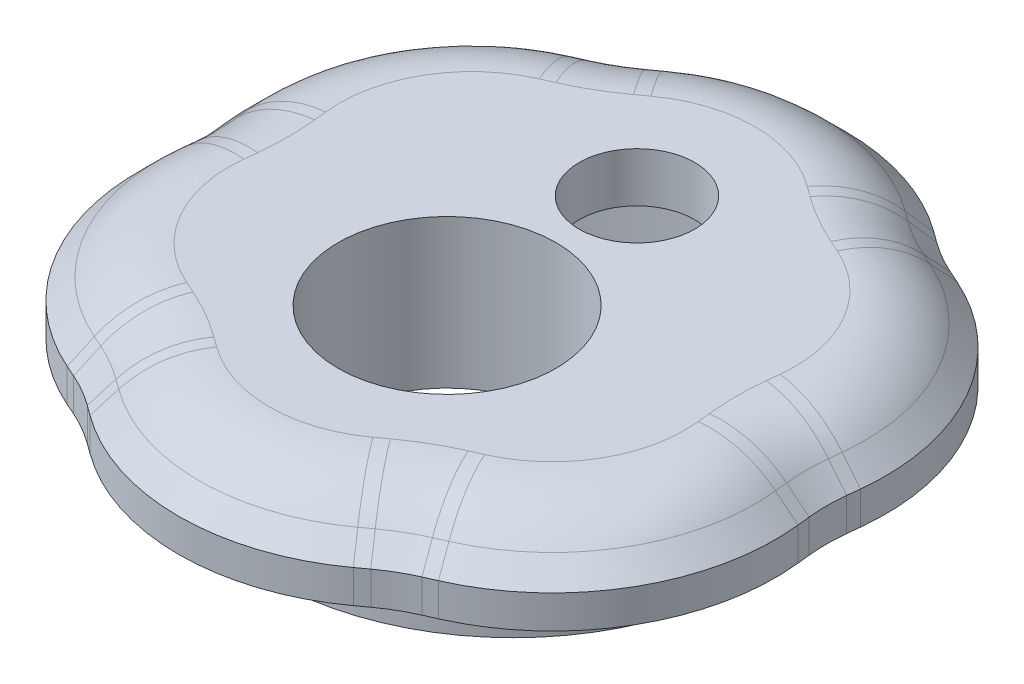
SolidWorks part; units mm, degrees
ref_plane "前基準面" through (0, 0, 0) normal (0, 0, 1) x (1, 0, 0)
ref_plane "上基準面" through (0, 0, 0) normal (0, 1, 0) x (1, 0, 0)
ref_plane "右基準面" through (0, 0, 0) normal (1, 0, 0) x (0, 0, -1)
sketch "草圖1" plane through (0, 0, 0) normal (0, 1, 0) x (1, 0, 0)
  line L14 (-20.7719, 1.7234) -> (-20.6902, 0.9708)
  line L19 (-20.6902, -0.9731) -> (-20.7719, -1.7257)
  line L20 (-11.9129, -17.0699) -> (-11.2203, -17.3754)
  line L21 (-9.5368, -18.3474) -> (-8.926, -18.7945)
  line L22 (8.7921, -18.7945) -> (9.4029, -18.3474)
  line L23 (11.0864, -17.3754) -> (11.779, -17.0699)
  line L24 (20.638, -1.7257) -> (20.5563, -0.9731)
  line L25 (20.5563, 0.9708) -> (20.638, 1.7234)
  line L26 (11.779, 17.0676) -> (11.0864, 17.3731)
  line L27 (9.4029, 18.3451) -> (8.7921, 18.7921)
  line L28 (-8.926, 18.7921) -> (-9.5368, 18.3451)
  line L29 (-11.2203, 17.3731) -> (-11.9129, 17.0676)
  arc A13 (-11.9129, 17.0676) -> (-20.7719, 1.7234) centre (-5.8597, 3.3433) ccw
  arc A14 (-20.6902, 0.9708) -> (-20.6902, -0.9731) centre (-29.6375, -0.0012) cw
  arc A15 (-20.7719, -1.7257) -> (-11.9129, -17.0699) centre (-5.8597, -3.3456) ccw
  arc A16 (-9.5368, -18.3474) -> (-11.2203, -17.3754) centre (-14.8522, -25.61) ccw
  arc A17 (-8.926, -18.7945) -> (8.7921, -18.7945) centre (-0.0669, -6.69) ccw
  arc A18 (11.0864, -17.3754) -> (9.4029, -18.3474) centre (14.7184, -25.61) ccw
  arc A19 (11.779, -17.0699) -> (20.638, -1.7257) centre (5.7258, -3.3456) ccw
  arc A20 (20.5563, 0.9708) -> (20.5563, -0.9731) centre (29.5037, -0.0012) ccw
  arc A21 (20.638, 1.7234) -> (11.779, 17.0676) centre (5.7258, 3.3433) ccw
  arc A22 (9.4029, 18.3451) -> (11.0864, 17.3731) centre (14.7184, 25.6077) ccw
  arc A23 (8.7921, 18.7921) -> (-8.926, 18.7921) centre (-0.0669, 6.6877) ccw
  arc A24 (-11.2203, 17.3731) -> (-9.5368, 18.3451) centre (-14.8522, 25.6077) ccw
  point P20 (-0.0509, -0.0012)
  dimension "D1" = 6.6888
  dimension "D2" = 6.69
extrude "填料-伸長1" add sketch "草圖1" along normal blind 3
chamfer "導角1" distance 4.5 angle 45 24 edges at (-0.0669, 3, -21.6877) (-9.2314, 3, -18.5686) (9.0975, 3, -18.5686) (-10.3522, 3, -17.8135) (10.2184, 3, -17.8135) (-11.5666, 3, -17.2204) (11.4327, 3, -17.2204) (-18.85, 3, -10.8433) (18.7161, 3, -10.8433) (-20.731, 3, -1.3471) (20.5972, 3, -1.3471) (-20.6375, 3, 0.0012) (20.5037, 3, 0.0012) (-20.731, 3, 1.3494) (20.5972, 3, 1.3494) (-18.85, 3, 10.8456) (18.7161, 3, 10.8456) (-11.5666, 3, 17.2227) (11.4327, 3, 17.2227) (-10.3522, 3, 17.8158) (10.2184, 3, 17.8158) (-9.2314, 3, 18.5709) (9.0975, 3, 18.5709) (-0.0669, 3, 21.69)
sketch "草圖3" plane through (0, 0, 0) normal (0, -1, 0) x (1, 0, 0)
  circle A0 centre (0, 0) radius 14.75
  circle A1 centre (0, 0) radius 14
  dimension "D1" = 29.5
  dimension "D2" = 28
extrude "填料-伸長2" add sketch "草圖3" along normal blind 6
fillet "圓角1" radius 6 24 edges at (-6.5737, 3, 14.9396) (-8.1022, 3, 13.9187) (-9.7506, 3, 13.1054) (-14.9529, 3, 8.5956) (-16.2574, 3, 1.8354) (-16.1375, 3, 0.0012) (-16.2574, 3, -1.833) (-14.9529, 3, -8.5933) (-9.7506, 3, -13.1031) (-8.1022, 3, -13.9164) (-6.5737, 3, -14.9373) (-0.0669, 3, -17.1877) (6.4398, 3, -14.9373) (7.9684, 3, -13.9164) (9.6167, 3, -13.1031) (14.819, 3, -8.5933) (16.1235, 3, -1.833) (16.0037, 3, 0.0012) (16.1235, 3, 1.8354) (14.819, 3, 8.5956) (9.6167, 3, 13.1054) (7.9684, 3, 13.9187) (6.4398, 3, 14.9396) (-0.0669, 3, 17.19)
sketch "草圖4" plane through (0, 3, 0) normal (0, 1, 0) x (1, 0, 0)
  circle A0 centre (0, -4) radius 6.6
  circle A1 centre (0, 7.5) radius 3.5
  dimension "D1" = 4
  dimension "D2" = 7
  dimension "D3" = 11.5
  dimension "D4" = 13.2
extrude "除料-伸長1" cut sketch "草圖4" against normal blind 10
sketch "草圖5" plane through (0, 0, 0) normal (0, -1, 0) x (1, 0, 0)
  circle A0 centre (0, 4) radius 6.6
  circle A1 centre (0, 4) radius 7.5
  dimension "D1" = 15
extrude "填料-伸長3" add sketch "草圖5" along normal blind 6
sketch "草圖6" plane through (0, 0, 0) normal (0, -1, 0) x (1, 0, 0)
  line L12 (-8.0603, -16.3276) -> (-7.4495, -16.7747)
  line L13 (7.3156, -16.7747) -> (7.9264, -16.3276)
  line L14 (10.0775, -15.0857) -> (10.7701, -14.7802)
  line L15 (18.1527, -1.9933) -> (18.0709, -1.2408)
  line L16 (18.0709, 1.2431) -> (18.1527, 1.9957)
  line L17 (10.7701, 14.7825) -> (10.0775, 15.088)
  line L18 (7.9264, 16.33) -> (7.3156, 16.777)
  line L19 (-7.4495, 16.777) -> (-8.0603, 16.33)
  line L20 (-10.2114, 15.088) -> (-10.904, 14.7825)
  line L21 (-18.2865, 1.9957) -> (-18.2048, 1.2431)
  line L22 (-18.2048, -1.2408) -> (-18.2865, -1.9933)
  line L23 (-10.904, -14.7802) -> (-10.2114, -15.0857)
  line L24 (-8.6509, -17.1346) -> (-8.0401, -17.5817)
  line L25 (7.9062, -17.5817) -> (8.517, -17.1346)
  line L26 (10.4811, -16.0007) -> (11.1737, -15.6952)
  line L27 (19.1468, -1.8853) -> (19.0651, -1.1328)
  line L28 (19.0651, 1.1351) -> (19.1468, 1.8877)
  line L29 (11.1737, 15.6975) -> (10.4811, 16.003)
  line L30 (8.517, 17.1369) -> (7.9062, 17.584)
  line L31 (-8.0401, 17.584) -> (-8.6509, 17.1369)
  line L32 (-10.615, 16.003) -> (-11.3076, 15.6975)
  line L33 (-19.2807, 1.8877) -> (-19.1989, 1.1351)
  line L34 (-19.1989, -1.1328) -> (-19.2807, -1.8853)
  line L35 (-11.3076, -15.6952) -> (-10.615, -16.0007)
  line L36 (-8.6509, -17.1346) -> (-8.0401, -17.5817)
  line L37 (7.9062, -17.5817) -> (8.517, -17.1346)
  line L38 (10.4811, -16.0007) -> (11.1737, -15.6952)
  line L39 (19.1468, -1.8853) -> (19.0651, -1.1328)
  line L40 (19.0651, 1.1351) -> (19.1468, 1.8877)
  line L41 (11.1737, 15.6975) -> (10.4811, 16.003)
  line L42 (8.517, 17.1369) -> (7.9062, 17.584)
  line L43 (-8.0401, 17.584) -> (-8.6509, 17.1369)
  line L44 (-10.615, 16.003) -> (-11.3076, 15.6975)
  line L45 (-19.2807, 1.8877) -> (-19.1989, 1.1351)
  line L46 (-19.1989, -1.1328) -> (-19.2807, -1.8853)
  line L47 (-11.3076, -15.6952) -> (-10.615, -16.0007)
  arc A12 (-7.4495, -16.7747) -> (7.3156, -16.7747) centre (-0.0669, -6.6877) ccw
  arc A13 (10.0775, -15.0857) -> (7.9264, -16.3276) centre (14.7184, -25.6077) ccw
  arc A14 (10.7701, -14.7802) -> (18.1527, -1.9933) centre (5.7258, -3.3433) ccw
  arc A15 (18.0709, 1.2431) -> (18.0709, -1.2408) centre (29.5037, 0.0012) ccw
  arc A16 (18.1527, 1.9957) -> (10.7701, 14.7825) centre (5.7258, 3.3456) ccw
  arc A17 (7.9264, 16.33) -> (10.0775, 15.088) centre (14.7184, 25.61) ccw
  arc A18 (7.3156, 16.777) -> (-7.4495, 16.777) centre (-0.0669, 6.69) ccw
  arc A19 (-10.2114, 15.088) -> (-8.0603, 16.33) centre (-14.8522, 25.61) ccw
  arc A20 (-10.904, 14.7825) -> (-18.2865, 1.9957) centre (-5.8597, 3.3456) ccw
  arc A21 (-18.2048, -1.2408) -> (-18.2048, 1.2431) centre (-29.6375, 0.0012) ccw
  arc A22 (-18.2865, -1.9933) -> (-10.904, -14.7802) centre (-5.8597, -3.3433) ccw
  arc A23 (-8.0603, -16.3276) -> (-10.2114, -15.0857) centre (-14.8522, -25.6077) ccw
  arc A24 (-8.0401, -17.5817) -> (7.9062, -17.5817) centre (-0.0669, -6.6877) ccw
  arc A25 (10.4811, -16.0007) -> (8.517, -17.1346) centre (14.7184, -25.6077) ccw
  arc A26 (11.1737, -15.6952) -> (19.1468, -1.8853) centre (5.7258, -3.3433) ccw
  arc A27 (19.0651, 1.1351) -> (19.0651, -1.1328) centre (29.5037, 0.0012) ccw
  arc A28 (19.1468, 1.8877) -> (11.1737, 15.6975) centre (5.7258, 3.3456) ccw
  arc A29 (8.517, 17.1369) -> (10.4811, 16.003) centre (14.7184, 25.61) ccw
  arc A30 (7.9062, 17.584) -> (-8.0401, 17.584) centre (-0.0669, 6.69) ccw
  arc A31 (-10.615, 16.003) -> (-8.6509, 17.1369) centre (-14.8522, 25.61) ccw
  arc A32 (-11.3076, 15.6975) -> (-19.2807, 1.8877) centre (-5.8597, 3.3456) ccw
  arc A33 (-19.1989, -1.1328) -> (-19.1989, 1.1351) centre (-29.6375, 0.0012) ccw
  arc A34 (-19.2807, -1.8853) -> (-11.3076, -15.6952) centre (-5.8597, -3.3433) ccw
  arc A35 (-8.6509, -17.1346) -> (-10.615, -16.0007) centre (-14.8522, -25.6077) ccw
  arc A36 (-8.0401, -17.5817) -> (7.9062, -17.5817) centre (-0.0669, -6.6877) ccw
  arc A37 (10.4811, -16.0007) -> (8.517, -17.1346) centre (14.7184, -25.6077) ccw
  arc A38 (11.1737, -15.6952) -> (19.1468, -1.8853) centre (5.7258, -3.3433) ccw
  arc A39 (19.0651, 1.1351) -> (19.0651, -1.1328) centre (29.5037, 0.0012) ccw
  arc A40 (19.1468, 1.8877) -> (11.1737, 15.6975) centre (5.7258, 3.3456) ccw
  arc A41 (8.517, 17.1369) -> (10.4811, 16.003) centre (14.7184, 25.61) ccw
  arc A42 (7.9062, 17.584) -> (-8.0401, 17.584) centre (-0.0669, 6.69) ccw
  arc A43 (-10.615, 16.003) -> (-8.6509, 17.1369) centre (-14.8522, 25.61) ccw
  arc A44 (-11.3076, 15.6975) -> (-19.2807, 1.8877) centre (-5.8597, 3.3456) ccw
  arc A45 (-19.1989, -1.1328) -> (-19.1989, 1.1351) centre (-29.6375, 0.0012) ccw
  arc A46 (-19.2807, -1.8853) -> (-11.3076, -15.6952) centre (-5.8597, -3.3433) ccw
  arc A47 (-8.6509, -17.1346) -> (-10.615, -16.0007) centre (-14.8522, -25.6077) ccw
  dimension "D1" = 0
  dimension "D2" = 1
extrude "填料-伸長4" add sketch "草圖6" along normal blind 2
